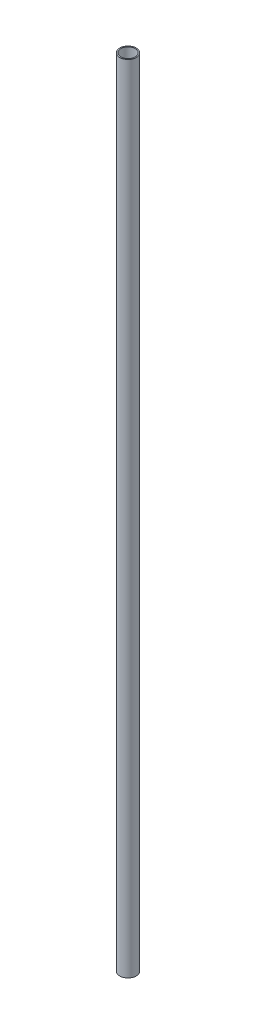
SolidWorks part; units mm, degrees
material "6061-T6 (SS)"
ref_plane "Front Plane" through (0, 0, 0) normal (0, 0, 1) x (1, 0, 0)
ref_plane "Top Plane" through (0, 0, 0) normal (0, 1, 0) x (1, 0, 0)
ref_plane "Right Plane" through (0, 0, 0) normal (1, 0, 0) x (0, 0, -1)
sketch "Sketch1" plane through (0, 0, 0) normal (0, 1, 0) x (1, 0, 0)
  circle A0 centre (0, 0) radius 9.525
  circle A1 centre (0, 0) radius 8.2804
  dimension "D1" = 19.05
  dimension "D2" = 16.5608
extrude "Boss-Extrude1" add sketch "Sketch1" along normal blind 914.4
ref_point "Point2"
ref_axis "Axis1" through (0, 914.4, 0) along (0, -1, 0)
